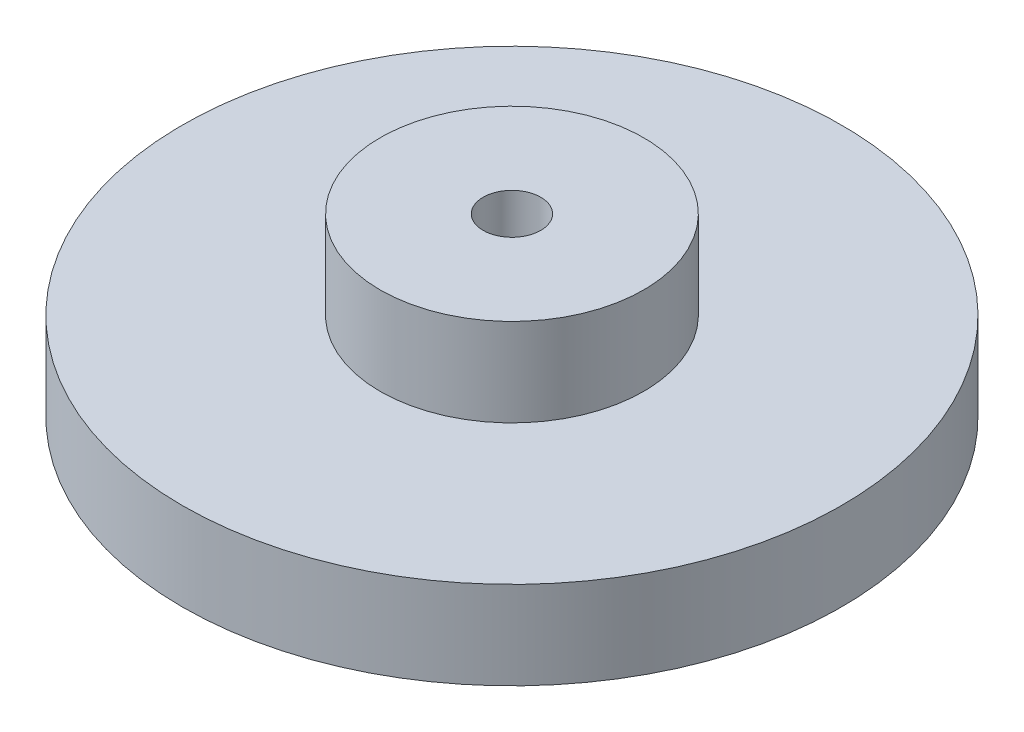
SolidWorks part; units mm, degrees
material "Silicon Dioxide"
ref_plane "Front Plane" through (0, 0, 0) normal (0, 0, 1) x (1, 0, 0)
ref_plane "Top Plane" through (0, 0, 0) normal (0, 1, 0) x (1, 0, 0)
ref_plane "Right Plane" through (0, 0, 0) normal (1, 0, 0) x (0, 0, -1)
sketch "Sketch1" plane through (0, 0, 0) normal (0, 1, 0) x (1, 0, 0)
  circle A0 centre (0, 0) radius 7.5
  dimension "D1" = 15
extrude "Boss-Extrude1" add sketch "Sketch1" along normal blind 2
sketch "Sketch2" plane through (0, 2, 0) normal (0, 1, 0) x (1, 0, 0)
  circle A0 centre (0, 0) radius 3
  dimension "D1" = 6
extrude "Boss-Extrude2" add sketch "Sketch2" along normal blind 2
sketch "Sketch3" plane through (0, 4, 0) normal (0, 1, 0) x (1, 0, 0)
  circle A0 centre (0, 0) radius 0.655
  dimension "D1" = 1.31
extrude "Cut-Extrude1" cut sketch "Sketch3" against normal blind 2.89
sketch "Sketch4" plane through (0, 1.11, 0) normal (0, 1, 0) x (1, 0, 0)
  circle A0 centre (0, 0) radius 0.655
extrude "Cut-Extrude3" cut sketch "Sketch4" against normal blind 1.11 draft 60 draft outward yes
